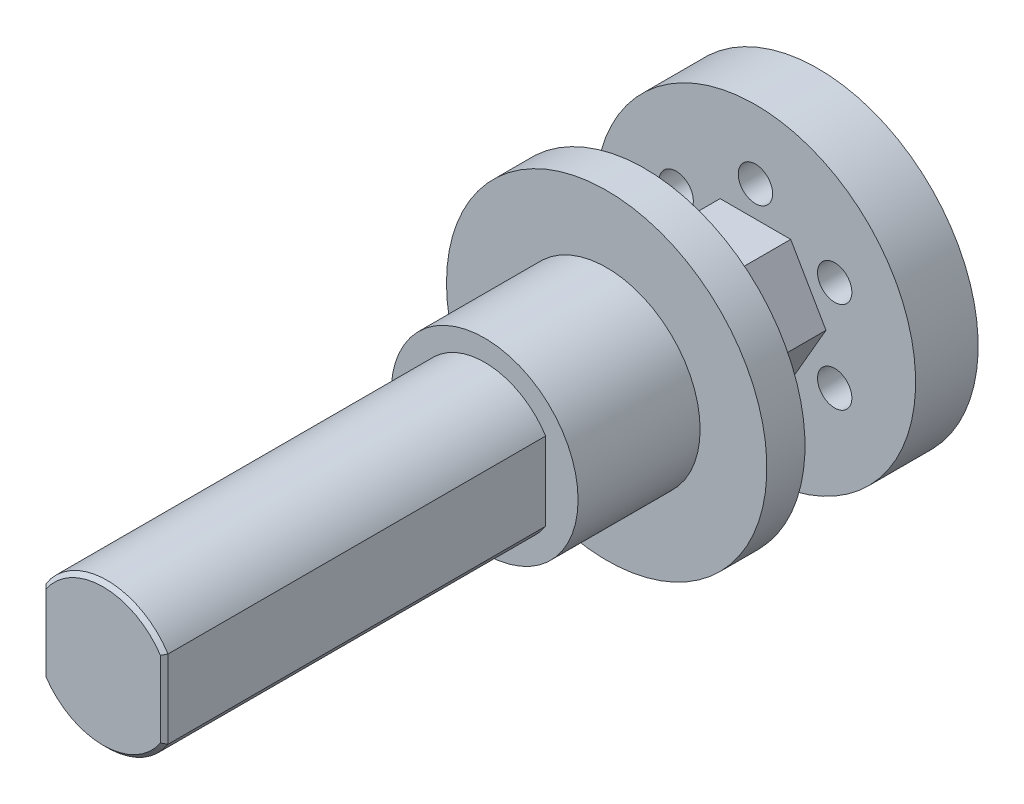
SolidWorks part; units mm, degrees
ref_plane "前视基准面" through (0, 0, 0) normal (0, 0, 1) x (1, 0, 0)
ref_plane "上视基准面" through (0, 0, 0) normal (0, 1, 0) x (1, 0, 0)
ref_plane "右视基准面" through (0, 0, 0) normal (1, 0, 0) x (0, 0, -1)
other "Configuration Table"
sketch "草图1" plane through (0, 0, 0) normal (0, 0, 1) x (1, 0, 0)
  circle A0 centre (0, 0) radius 9.25
  dimension "D1" = 18.5
extrude "凸台-拉伸1" add sketch "草图1" along normal blind 89.5 contours A0
ref_plane "基准面1" through (11.75, 0, 0) normal (-1, 0, 0) x (0, 0, 1)
ref_plane "基准面2" through (0, 0, 39.5) normal (0, 0, 1) x (1, 0, 0)
sketch "草图4" plane through (0, 0, 39.5) normal (0, 0, 1) x (1, 0, 0)
  circle A0 centre (0, 0) radius 12.25
  dimension "D1" = 24.5
extrude "凸台-拉伸2" add sketch "草图4" against normal blind 16
sketch "草图5" plane through (0, 0, 23.5) normal (0, 0, -1) x (-1, 0, 0)
  circle A0 centre (0, 0) radius 21
  dimension "D1" = 42
extrude "凸台-拉伸3" add sketch "草图5" along normal blind 5
sketch "草图6" plane through (0, 0, 0) normal (0, 0, -1) x (-1, 0, 0)
  circle A0 centre (0, 0) radius 21
  circle A1 centre (0, 0) radius 12 construction
  circle A2 centre (0, 12) radius 2.25
  circle A3 centre (0, 0) radius 21
  circle A4 centre (0, 0) radius 21
  circle A5 centre (0, 0) radius 21
  circle A6 centre (0, 0) radius 21
  circle A7 centre (0, 0) radius 21
  circle A8 centre (10.3923, 6) radius 2.25
  circle A9 centre (10.3923, -6) radius 2.25
  circle A10 centre (0, -12) radius 2.25
  circle A11 centre (-10.3923, -6) radius 2.25
  circle A12 centre (-10.3923, 6) radius 2.25
  point P14 (0, 0)
  point P25 (0, 0)
  dimension "D1" = 42
  dimension "D2" = 24
  dimension "D3" = 4.5
  dimension "D4" = 6
  dimension "D5" = 6
extrude "凸台-拉伸4" add sketch "草图6" along normal blind 4.2 and the other way blind 4 contours A0 | A12 | A2 | A8 | A9 | A10 | A11
sketch "草图7" plane through (0, 0, -4.2) normal (0, 0, -1) x (-1, 0, 0)
  circle A0 centre (0, 0) radius 20
  dimension "D1" = 40
extrude "切除-拉伸1" cut sketch "草图7" against normal blind 2
sketch "草图8" plane through (0, 0, 18.5) normal (0, 0, -1) x (-1, 0, 0)
  line L0 (-9.25, 0) -> (-4.625, -8.0107)
  line L1 (-4.625, -8.0107) -> (4.625, -8.0107)
  line L2 (4.625, -8.0107) -> (9.25, 0)
  line L3 (9.25, 0) -> (4.625, 8.0107)
  line L4 (4.625, 8.0107) -> (-4.625, 8.0107)
  line L5 (-4.625, 8.0107) -> (-9.25, 0)
  circle A0 centre (0, 0) radius 9.25 construction
  dimension "D1" = 18.5
  dimension "D2" = 120
extrude "切除-拉伸4" cut sketch "草图8" along normal up to surface (14.5 mm away) flip side to cut up to face at (-9.25, 0, 4)
sketch "草图11" plane through (0, 0, 39.5) normal (0, 0, 1) x (1, 0, 0)
  circle A0 centre (0, 0) radius 9.5
  dimension "D1" = 19
extrude "凸台-拉伸5" add sketch "草图11" along normal up to surface (50 mm away) up to face at (9.25, 0, 89.5)
sketch "草图13" plane through (0, 0, 89.5) normal (0, 0, 1) x (1, 0, 0)
  line L0 (-8, 5.1235) -> (-8, -5.1235)
  line L1 (-8, -5.1235) -> (8, -5.1235) construction
  line L2 (8, -5.1235) -> (8, 5.1235)
  line L3 (8, 5.1235) -> (-8, 5.1235) construction
  circle A0 centre (0, 0) radius 9.5 construction
  circle A1 centre (0, 0) radius 9.5 construction
  arc A2 (-8, 5.1235) -> (8, 5.1235) centre (0, 0) cw
  arc A3 (-8, -5.1235) -> (8, -5.1235) centre (0, 0) ccw
  dimension "D1" = 8
extrude "切除-拉伸-薄壁1" cut sketch "草图13" against normal up to surface (50 mm away) flip side to cut thin up to face at (9.5, 0, 39.5) thin type one direction wall 10
chamfer "倒角1" distance 0.5 angle 45 4 edges at (8, 0, 89.5) (0, -9.5, 89.5) (-8, 0, 89.5) (0, 9.5, 89.5)
